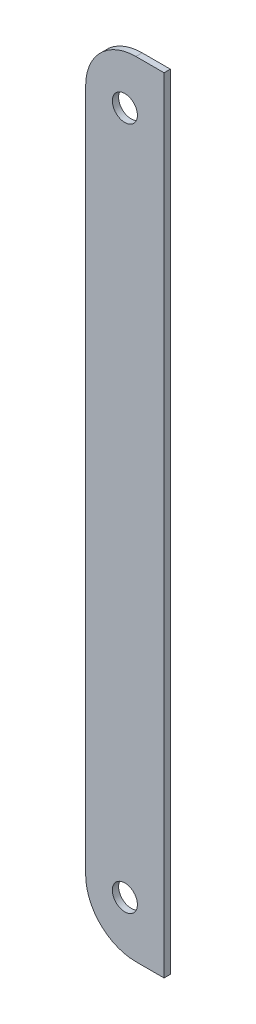
SolidWorks part; units mm, degrees
ref_plane "Front Plane" through (0, 0, 0) normal (0, 0, 1) x (1, 0, 0)
ref_plane "Top Plane" through (0, 0, 0) normal (0, 1, 0) x (1, 0, 0)
ref_plane "Right Plane" through (0, 0, 0) normal (1, 0, 0) x (0, 0, -1)
sketch "Sketch1" plane through (0, 0, 0) normal (0, 0, 1) x (1, 0, 0)
  line L0 (-12.5, 0) -> (12.5, 0) construction
  line L1 (3.5, 125) -> (12.5, 125)
  line L2 (-12.5, 109) -> (-12.5, -109)
  line L3 (3.5, -125) -> (12.5, -125)
  line L4 (12.5, 125) -> (12.5, -125)
  line L5 (-12.5, 125) -> (12.5, -125) construction
  line L6 (-12.5, -125) -> (12.5, 125) construction
  line L7 (-12.5, 109) -> (-12.5, 125) construction
  line L8 (-12.5, 125) -> (3.5, 125) construction
  line L9 (-12.5, 109) -> (-12.5, 125) construction
  circle A0 centre (0, 109) radius 4
  circle A1 centre (0, -109) radius 4
  arc A2 (3.5, 125) -> (-12.5, 109) centre (3.5, 109) ccw
  arc A3 (-12.5, -109) -> (3.5, -125) centre (3.5, -109) ccw
  point P0 (0, 0)
  dimension "D4" = 8
  dimension "D5" = 16
  dimension "D2" = 16
  dimension "D1" = 25
  dimension "D3" = 218
  dimension "D6" = 250
extrude "Boss-Extrude1" add sketch "Sketch1" along normal blind 2
